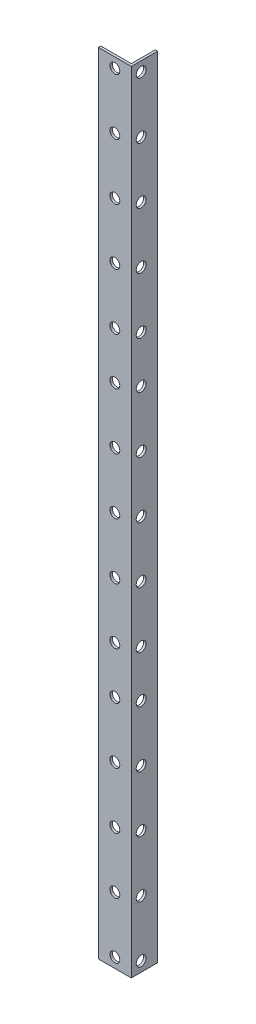
SolidWorks part; units mm, degrees
material "6061-T6 (SS)"
ref_plane "Alzado" through (0, 0, 0) normal (0, 0, 1) x (1, 0, 0)
ref_plane "Planta" through (0, 0, 0) normal (0, 1, 0) x (1, 0, 0)
ref_plane "Vista lateral" through (0, 0, 0) normal (1, 0, 0) x (0, 0, -1)
sketch "Sketch1" plane through (0, 0, 0) normal (0, 1, 0) x (1, 0, 0)
  line L0 (0, 0) -> (15, 0)
  line L1 (15, 0) -> (15, 12)
  line L2 (15, 12) -> (13.9, 12)
  line L3 (13.9, 12) -> (13.9, 1.1)
  line L4 (13.9, 1.1) -> (0, 1.1)
  line L5 (0, 1.1) -> (0, 0)
  dimension "D1" = 15
  dimension "D2" = 12
  dimension "D3" = 1.1
  dimension "D4" = 1.1
extrude "Boss-Extrude1" add sketch "Sketch1" along normal blind 360
sketch "Sketch2" plane through (13.9, 0, 0) normal (-1, 0, 0) x (0, 0, 1)
  circle A1 centre (-4.5, 329.8125) radius 2.25
  circle A2 centre (-4.5, 304.125) radius 2.25
  circle A3 centre (-4.5, 278.4375) radius 2.25
  circle A4 centre (-4.5, 252.75) radius 2.25
  circle A5 centre (-4.5, 231.375) radius 2.25
  circle A6 centre (-4.5, 205.6875) radius 2.25
  circle A7 centre (-4.5, 180) radius 2.25
  circle A8 centre (-4.5, 154.3125) radius 2.25
  circle A9 centre (-4.5, 128.625) radius 2.25
  circle A10 centre (-4.5, 107.25) radius 2.25
  circle A11 centre (-4.5, 81.5625) radius 2.25
  circle A12 centre (-4.5, 55.875) radius 2.25
  circle A13 centre (-4.5, 30.1875) radius 2.25
  circle A14 centre (-4.5, 4.5) radius 2.25
  circle A15 centre (-4.5, 355.5) radius 2.25
  dimension "D1" = 4.5
extrude "Cut-Extrude1" cut sketch "Sketch2" against normal up to next
sketch "Sketch3" plane through (0, 0, 0) normal (0, 0, 1) x (1, 0, 0)
  line L0 (-218, 242.75) -> (18, 242.75) construction
  line L2 (18, 363) -> (18, -3) construction
  line L3 (-65, 263) -> (-10, 263) construction
  line L4 (-10, 222.5) -> (-65, 222.5) construction
  line L5 (-218, 117.25) -> (18, 117.25) construction
  line L6 (-218, -3) -> (-218, 363) construction
  line L7 (-65, 137.5) -> (-10, 137.5) construction
  line L8 (-10, 97) -> (-65, 97) construction
  circle A15 centre (7.5, 355.5) radius 2.25
  dimension "D1" = 4.5
extrude "Cut-Extrude2" cut sketch "Sketch3" against normal up to next
sketch "Sketch4" plane through (0, 0, 0) normal (0, 0, 1) x (1, 0, 0)
  line L0 (18, 242.75) -> (-100, 242.75) construction
  line L1 (-218, 242.75) -> (18, 242.75) construction
  line L2 (18, 117.25) -> (-100, 117.25) construction
  line L3 (-218, 117.25) -> (18, 117.25) construction
pattern_linear "LPattern1" count 5 spacing 25.6562 along (0, -1, 0) of "Cut-Extrude2"
pattern_linear "LPattern2" count 3 spacing 124.1875 along (0, -1, 0) of "LPattern1"
